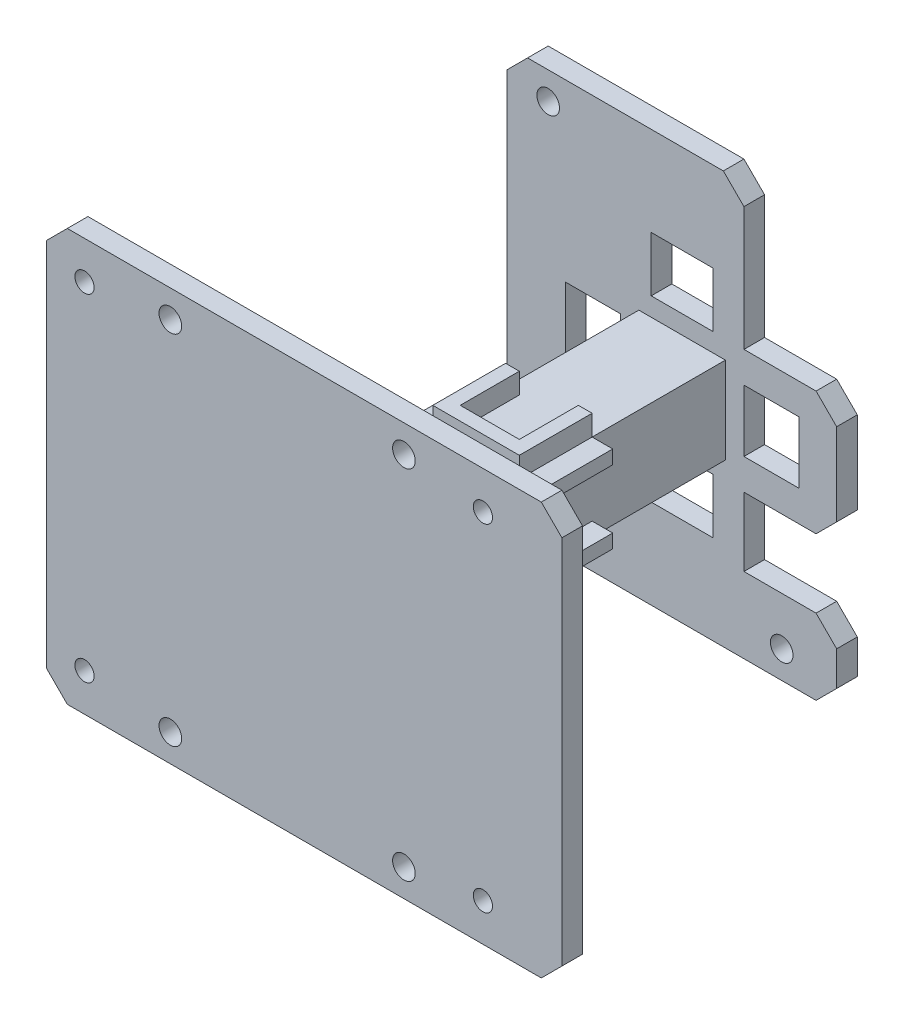
SolidWorks part; units mm, degrees
ref_plane "前视基准面" through (0, 0, 0) normal (0, 0, 1) x (1, 0, 0)
ref_plane "上视基准面" through (0, 0, 0) normal (0, 1, 0) x (1, 0, 0)
ref_plane "右视基准面" through (0, 0, 0) normal (1, 0, 0) x (0, 0, -1)
sketch "草图4" plane through (0, 0, 0) normal (0, 0, 1) x (1, 0, 0)
  line L0 (5, 19) -> (5, 30)
  line L1 (-39, 30) -> (5, 30)
  line L3 (-39, -30) -> (20, -30)
  line L6 (5, 19) -> (5, -19)
  line L7 (5, 18) -> (-43, -20.4) construction
  line L24 (-39, 30) -> (-43, 30)
  line L27 (-43, -30) -> (-39, -30)
  line L35 (5, -19) -> (20, -19)
  line L36 (20, -19) -> (20, -30)
  line L38 (-43, 30) -> (-43, -30)
  line L39 (-43, 20.4) -> (20, -30) construction
  circle A2 centre (-3, 26) radius 1.65
  circle A3 centre (-37, 26) radius 1.65
  circle A4 centre (-37, -26) radius 1.65
  circle A5 centre (-3, -26) radius 1.65
  circle A6 centre (8.5, -24.5) radius 1.4
  circle A9 centre (-3, 26) radius 2.5 construction
  point P0 (0, 0)
  dimension "D9" = 3.3
  dimension "D10" = 3.3
  dimension "D15" = 5
  dimension "D11" = 11
  dimension "D13" = 34
extrude "凸台-拉伸1" add sketch "草图4" along normal blind 3
sketch "草图5" plane through (0, 0, 3) normal (0, 0, 1) x (1, 0, 0)
  line L0 (-43, 30) -> (8, -30) construction
  line L1 (5, 30) -> (-43, -30) construction
  line L3 (-23.8, 6.3) -> (-11.2, 6.3)
  line L5 (5, 30) -> (-43, 30)
  line L6 (-43, 30) -> (-43, -30)
  line L7 (-43, -30) -> (20, -30)
  line L9 (5, 30) -> (-43, 30)
  line L11 (-43, -30) -> (20, -30)
  line L12 (-23.8, 6.3) -> (-23.8, -6.3)
  line L13 (-23.8, -6.3) -> (-11.2, -6.3)
  line L14 (-11.2, 6.3) -> (-11.2, -6.3)
  line L15 (-23.8, 6.3) -> (-11.2, -6.3) construction
  line L16 (-23.8, -6.3) -> (-11.2, 6.3) construction
  line L19 (-11.2, 6.3) -> (-13.96, 6.3)
  line L21 (-12.145, -6.3) -> (-11.2, -6.3)
  line L23 (20, -30) -> (20, -19)
  line L25 (-23.8, -6.3) -> (-24.04, -6.3)
  line L26 (20, -30) -> (20, -19)
  line L27 (-22.855, 6.3) -> (-23.8, 6.3)
  line L30 (20, -19) -> (5, -19)
  line L32 (5, -19) -> (5, 30)
  line L33 (5, -19) -> (5, 30)
  line L34 (20, -19) -> (5, -19)
  line L36 (-43, 30) -> (-43, -30)
  point P2 (-17.5, 0)
  dimension "D2" = 12.6
  dimension "D3" = 12.6
  dimension "D1" = 0
extrude "凸台-拉伸2" add sketch "草图5" along normal blind 30 contours L14 L3 L12 L13 region at (-17.5, 0, 3)
sketch "草图6" plane through (0, 0, 0) normal (0, 0, -1) x (-1, 0, 0)
  line L2 (13, 9) -> (13, 17)
  line L9 (13, 17) -> (22, 17)
  line L10 (22, 17) -> (22, 9)
  line L12 (34.5, 4.5) -> (34.5, -4.5)
  line L13 (34.5, -4.5) -> (26.5, -4.5)
  line L14 (22, -9) -> (22, -17)
  line L15 (22, -17) -> (13, -17)
  line L16 (13, -17) -> (13, -9)
  line L18 (0.5, -4.5) -> (0.5, 4.5)
  line L19 (0.5, 4.5) -> (8.5, 4.5)
  line L22 (13, 9) -> (22, 9)
  line L25 (26.5, 4.5) -> (26.5, -4.5)
  line L26 (13, -9) -> (22, -9)
  line L27 (8.5, -4.5) -> (8.5, 4.5)
  line L28 (8.5, -4.5) -> (0.5, -4.5)
  line L29 (26.5, 4.5) -> (34.5, 4.5)
  point P6 (17.5, 0)
  dimension "D14" = 8
  dimension "D15" = 8
  dimension "D16" = 8
  dimension "D17" = 8
extrude "切除-拉伸2" cut sketch "草图6" against normal through all
sketch "草图8" plane through (-11.2, 0, 0) normal (1, 0, 0) x (0, 0, -1)
  line L0 (-31, 4.3) -> (-22.4, 4.3)
  line L1 (-31, 4.3) -> (-31, -4.3)
  line L2 (-31, -4.3) -> (-22.4, -4.3)
  line L3 (-22.4, -4.3) -> (-22.4, -6.3)
  line L4 (-3, -6.3) -> (-3, 6.3)
  line L5 (-3, 6.3) -> (-33, 6.3)
  line L6 (-33, 6.3) -> (-33, -6.3)
  line L7 (-33, -6.3) -> (-3, -6.3)
  line L9 (-22.4, 6.3) -> (-33, 6.3)
  line L10 (-33, 6.3) -> (-33, -6.3)
  line L11 (-33, -6.3) -> (-22.4, -6.3)
  line L12 (-33, 0) -> (-20.4591, 0) construction
  line L13 (-22.4, 4.3) -> (-22.4, 6.3)
  point P10 (-31, 0)
  dimension "D2" = 2
  dimension "D3" = 2
  dimension "D4" = 8.6
  dimension "D1" = 0
extrude "凸台-拉伸3" add sketch "草图8" along normal blind 3
sketch "草图10" plane through (-23.8, 0, 0) normal (-1, 0, 0) x (0, 0, 1)
  line L0 (33, 0) -> (22.2066, 0) construction
  line L1 (22.4, 6.3) -> (22.4, 4.3)
  line L2 (22.4, 4.3) -> (31, 4.3)
  line L3 (31, 4.3) -> (31, -4.3)
  line L4 (3, 6.3) -> (3, -6.3)
  line L5 (3, -6.3) -> (33, -6.3)
  line L7 (33, 6.3) -> (3, 6.3)
  line L11 (33, 6.3) -> (22.4, 6.3)
  line L12 (22.4, -4.3) -> (31, -4.3)
  line L13 (22.4, -6.3) -> (22.4, -4.3)
  line L18 (22.4, -6.3) -> (33, -6.3)
  line L20 (33, -6.3) -> (33, 6.3)
  line L21 (33, -6.3) -> (33, 6.3)
  point P12 (31, 0)
  dimension "D2" = 2
  dimension "D4" = 8.6
  dimension "D1" = 0
extrude "凸台-拉伸4" add sketch "草图10" along normal blind 3
sketch "草图11" plane through (0, -6.3, 0) normal (0, -1, 0) x (1, 0, 0)
  line L0 (-23.8, 22.4) -> (-23.8, 33)
  line L1 (-11.2, 22.4) -> (-11.2, 33)
  line L2 (-17.5, 33.5045) -> (-17.5, 25.0515) construction
  line L3 (-23.8, 22.4) -> (-21.8, 22.4)
  line L4 (-21.8, 22.4) -> (-21.8, 31)
  line L5 (-21.8, 31) -> (-13.2, 31)
  line L6 (-13.2, 22.4) -> (-13.2, 31)
  line L7 (-11.2, 22.4) -> (-13.2, 22.4)
  line L9 (-11.2, 3) -> (-11.2, 22.4)
  line L10 (-23.8, 3) -> (-11.2, 3)
  line L11 (-11.2, 22.4) -> (-8.2, 22.4)
  line L12 (-8.2, 33) -> (-26.8, 33)
  line L15 (-23.8, 22.4) -> (-23.8, 3)
  line L20 (-11.2, 33) -> (-23.8, 33)
  line L24 (-26.8, 22.4) -> (-23.8, 22.4) construction
  line L31 (-8.2, 22.4) -> (-8.2, 33)
  line L32 (-26.8, 33) -> (-26.8, 22.4)
  line L33 (-26.8, 22.4) -> (-23.8, 22.4)
  point P17 (-17.5, 31)
  point P19 (-22.8, 22.4)
  dimension "D2" = 2
  dimension "D3" = 2
  dimension "D1" = 0
extrude "凸台-拉伸5" add sketch "草图11" along normal blind 3
sketch "草图12" plane through (0, 6.3, 0) normal (0, 1, 0) x (1, 0, 0)
  line L0 (-23.8, -22.4) -> (-23.8, -33)
  line L1 (-11.2, -22.4) -> (-11.2, -33)
  line L2 (-23.8, -22.4) -> (-21.8, -22.4)
  line L3 (-21.8, -22.4) -> (-21.8, -31)
  line L4 (-17.5, -33) -> (-17.5, -24.9016) construction
  line L5 (-21.8, -31) -> (-13.2, -31)
  line L6 (-13.2, -22.4) -> (-13.2, -31)
  line L7 (-11.2, -22.4) -> (-13.2, -22.4)
  line L8 (-11.2, -3) -> (-23.8, -3)
  line L9 (-23.8, -3) -> (-23.8, -22.4)
  line L12 (-26.8, -33) -> (-8.2, -33)
  line L13 (-23.8, -22.4) -> (-26.8, -22.4)
  line L15 (-11.2, -22.4) -> (-11.2, -3)
  line L20 (-23.8, -33) -> (-11.2, -33)
  line L29 (-26.8, -22.4) -> (-26.8, -33)
  line L30 (-8.2, -33) -> (-8.2, -22.4)
  line L31 (-8.2, -22.4) -> (-11.2, -22.4)
  point P17 (-17.5, -31)
  dimension "D2" = 2
  dimension "D3" = 2
  dimension "D1" = 0
extrude "凸台-拉伸6" add sketch "草图12" along normal blind 3
sketch "草图13" plane through (0, 0, 33) normal (0, 0, 1) x (1, 0, 0)
  line L0 (-23.8, 5.04) -> (-11.2, -5.04) construction
  line L1 (-11.2, 5.04) -> (-23.8, -5.04) construction
  line L3 (-23.8, 6.3) -> (-11.2, 6.3)
  line L12 (-23.8, 6.3) -> (-23.8, -6.3)
  line L13 (-23.8, -6.3) -> (-11.2, -6.3)
  line L14 (-11.2, 6.3) -> (-11.2, -6.3)
  line L15 (-23.8, 6.3) -> (-11.2, -6.3) construction
  line L16 (-23.8, -6.3) -> (-11.2, 6.3) construction
  point P2 (-17.5, 0)
  dimension "D2" = 12.6
  dimension "D3" = 12.6
extrude "凸台-拉伸7" add sketch "草图13" along normal blind 22
sketch "草图14" plane through (0, 0, 55) normal (0, 0, 1) x (1, 0, 0)
  line L0 (-55, 30) -> (20, -30) construction
  line L1 (-39, 30) -> (20, 30)
  line L3 (-39, -30) -> (20, -30)
  line L5 (-55, 30) -> (-48.1001, 24.4801) construction
  line L6 (-55, -30) -> (-48.1001, -24.4801) construction
  line L7 (20, 30) -> (-55, -30) construction
  line L13 (20, 30) -> (20, -30)
  line L24 (-39, 30) -> (-55, 30)
  line L27 (-55, -30) -> (-39, -30)
  line L37 (-55, 30) -> (-55, -30)
  circle A0 centre (-49.5, 24.5) radius 1.4
  circle A1 centre (8.5, 24.5) radius 1.4
  circle A2 centre (-3, 26) radius 1.65
  circle A3 centre (-37, 26) radius 1.65
  circle A4 centre (-37, -26) radius 1.65
  circle A5 centre (-3, -26) radius 1.65
  circle A6 centre (8.5, -24.5) radius 1.4
  circle A7 centre (-49.5, -24.5) radius 1.4
  circle A8 centre (8.5, 24.5) radius 2.5 construction
  circle A9 centre (-3, 26) radius 2.5 construction
  point P0 (0, 0)
  dimension "D3" = 2.8
  dimension "D4" = 2.8
  dimension "D9" = 3.3
  dimension "D10" = 3.3
  dimension "D15" = 5
  dimension "D16" = 5
  dimension "D1" = 75
  dimension "D2" = 60
  dimension "D6" = 58
  dimension "D7" = 5.5
  dimension "D8" = 5.5
  dimension "D13" = 34
extrude "凸台-拉伸8" add sketch "草图14" along normal blind 3
sketch "草图15" plane through (0, 0, 3) normal (0, 0, 1) x (1, 0, 0)
  line L0 (5, 30) -> (-8.5, 30)
  line L1 (-8.5, 30) -> (-8.5, 9)
  line L2 (-8.5, 9) -> (5, 9)
  line L3 (5, -9) -> (-8.5, -9)
  line L4 (5, 9) -> (5, 30)
  line L10 (5, -19) -> (5, 30)
  line L13 (5, 30) -> (-43, 30)
  line L14 (-43, 30) -> (-43, -30)
  line L15 (-43, -30) -> (20, -30)
  line L18 (5, -19) -> (5, -9)
  line L21 (5, 30) -> (-43, 30)
  line L23 (-43, -30) -> (20, -30)
  line L29 (20, -30) -> (20, -19)
  line L30 (20, -30) -> (20, -19)
  line L31 (20, -19) -> (5, -19)
  line L37 (-43, 30) -> (-43, -30)
  line L52 (-8.5, -9) -> (-8.5, -19)
  line L53 (-8.5, -19) -> (5, -19)
  line M51 (5, -19) -> (5, 30)
  dimension "D1" = 0
extrude "切除-拉伸3" cut sketch "草图15" against normal through all contours L1 L2 L0 M51 | L52 L53 L3 M51 region at (-1.75, 19.5, 3) region at (-1.75, -14, 3)
chamfer "倒角1" distance 3 angle 45 11 edges at (-43, -30, 1.5) (20, -30, 1.5) (20, -19, 1.5) (5, -9, 1.5) (5, 9, 1.5) (-43, 30, 1.5) (-8.5, 30, 1.5) (-55, 30, 56.5) (20, 30, 56.5) (20, -30, 56.5) (-55, -30, 56.5)
sketch "草图16" plane through (0, 0, 3) normal (0, 0, 1) x (1, 0, 0)
  line L0 (5, -19) -> (5, -30)
  line L17 (-43, 27) -> (-43, -27)
  line L18 (-43, -27) -> (-40, -30)
  line L19 (-40, -30) -> (17, -30)
  line L20 (17, -30) -> (20, -27)
  line L21 (20, -27) -> (20, -22)
  line L22 (20, -22) -> (17, -19)
  line L23 (17, -19) -> (-8.5, -19)
  line L24 (-8.5, -19) -> (-8.5, -9)
  line L25 (-8.5, -9) -> (2, -9)
  line L26 (2, -9) -> (5, -6)
  line L27 (5, -6) -> (5, 6)
  line L28 (5, 6) -> (2, 9)
  line L29 (2, 9) -> (-8.5, 9)
  line L30 (-8.5, 9) -> (-8.5, 27)
  line L31 (-8.5, 27) -> (-11.5, 30)
  line L32 (-11.5, 30) -> (-40, 30)
  line L33 (-40, 30) -> (-43, 27)
  line L36 (5, -30) -> (17, -30)
  line L37 (17, -30) -> (20, -27)
  line L38 (20, -27) -> (20, -22)
  line L39 (20, -22) -> (17, -19)
  line L40 (17, -19) -> (5, -19)
  dimension "D1" = 0
extrude "切除-拉伸4" cut sketch "草图16" against normal blind 10
chamfer "倒角2" distance 3 angle 45 2 edges at (5, -19, 1.5) (5, -30, 1.5)
